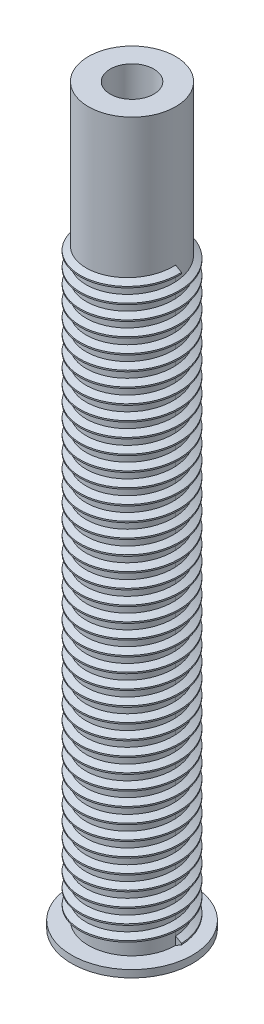
SolidWorks part; units mm, degrees
ref_plane "Front Plane" through (0, 0, 0) normal (0, 0, 1) x (1, 0, 0)
ref_plane "Top Plane" through (0, 0, 0) normal (0, 1, 0) x (1, 0, 0)
ref_plane "Right Plane" through (0, 0, 0) normal (1, 0, 0) x (0, 0, -1)
sketch "Sketch1" plane through (0, 0, 0) normal (0, 1, 0) x (1, 0, 0)
  circle A0 centre (0, 0) radius 6
  dimension "D1" = 12
extrude "Boss-Extrude1" add sketch "Sketch1" along normal blind 100
thread "Thread1" pitch 1.5 method extrude profile "Thread Profile1" start angle 0, offset 0, length 80, pitch 2, diameter 12
ref_plane "Plane1" through (6, 0, 0) normal (0, 0, 1) x (1, 0, 0)
sketch "Thread Profile1" plane through (6, 0, 0) normal (0, 0, 1) x (1, 0, 0)
  line L0 (0, 0) -> (0, 1.5) construction
  line L1 (0, 0) -> (0.8119, 0.4687)
  line L2 (0.8119, 0.4687) -> (0.8119, 0.6562)
  line L3 (0.8119, 0.6562) -> (0, 1.125)
  line L4 (0.8119, 0.5625) -> (0, 0.5625) construction
  line L11 (0, 0) -> (0, 1.125)
  point P2 (0, 0)
  dimension "Pitch" = 1.5
  dimension "Profile_Angle" = 60
  dimension "Profile_Land" = 0.1875
  dimension "Profile_Height" = 0.8119
sketch "Sketch4" plane through (0, 100, 0) normal (0, 1, 0) x (1, 0, 0)
  circle A0 centre (0, 0) radius 3
  dimension "D1" = 6
extrude "Cut-Extrude1" cut sketch "Sketch4" against normal blind 19
sketch "Sketch5" plane through (0, 0, 0) normal (0, -1, 0) x (1, 0, 0)
  circle A0 centre (0, 0) radius 8.3156
extrude "Boss-Extrude2" add sketch "Sketch5" along normal blind 1
